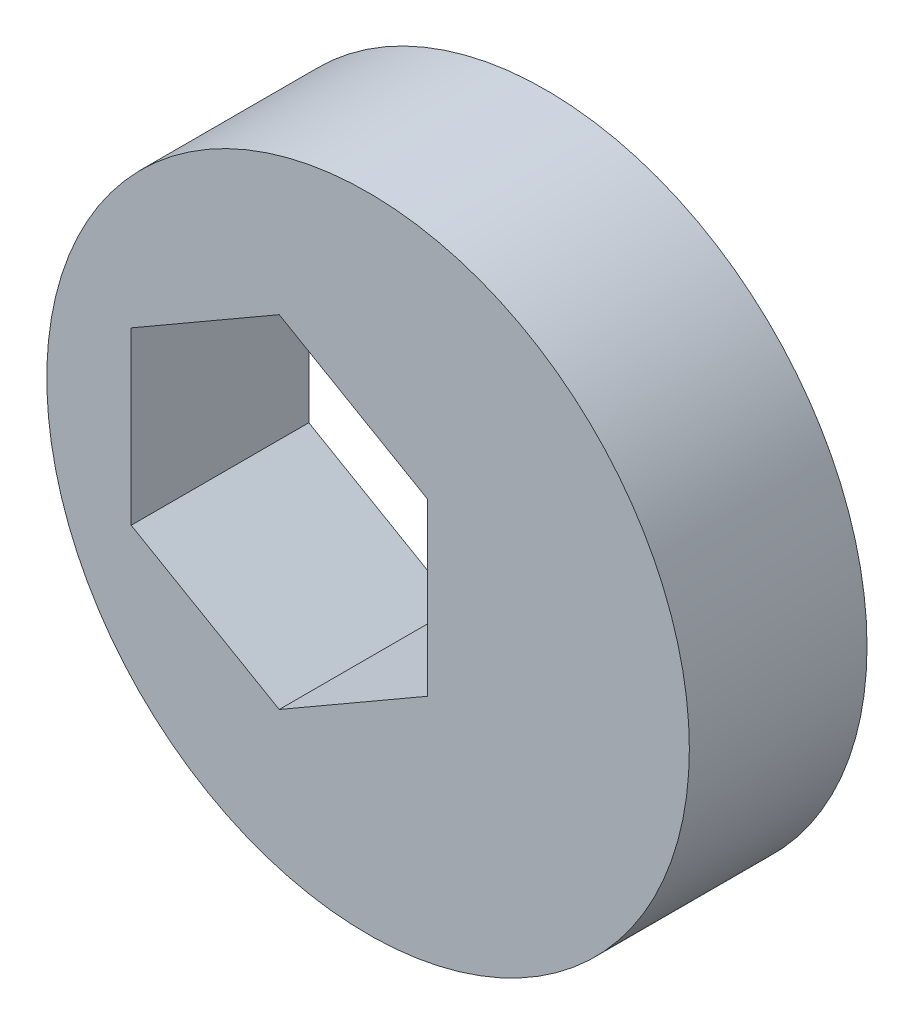
SolidWorks part; units mm, degrees
ref_plane "Front Plane" through (0, 0, 0) normal (0, 0, 1) x (1, 0, 0)
ref_plane "Top Plane" through (0, 0, 0) normal (0, 1, 0) x (1, 0, 0)
ref_plane "Right Plane" through (0, 0, 0) normal (1, 0, 0) x (0, 0, -1)
sketch "Sketch1" plane through (0, 0, 0) normal (0, 0, 1) x (1, 0, 0)
  line L0 (3, 0) -> (0, 0) construction
  line L2 (0, 5.7735) -> (-5, 2.8868)
  line L3 (-5, 2.8868) -> (-5, -2.8868)
  line L4 (-5, -2.8868) -> (0, -5.7735)
  line L5 (0, -5.7735) -> (5, -2.8868)
  line L6 (5, -2.8868) -> (5, 2.8868)
  line L7 (5, 2.8868) -> (0, 5.7735)
  circle A0 centre (3, 0) radius 10.85
  circle A1 centre (0, 0) radius 5 construction
  dimension "D1" = 21.7
  dimension "D2" = 3
  dimension "D3" = 10
extrude "Boss-Extrude1" add sketch "Sketch1" against normal blind 6
ref_axis "Axis1" through (0, 0, 5.6764) along (0, 0, -1)
scale "Scale1" scale about centroid uniform scaling yes scale factor 0.4
